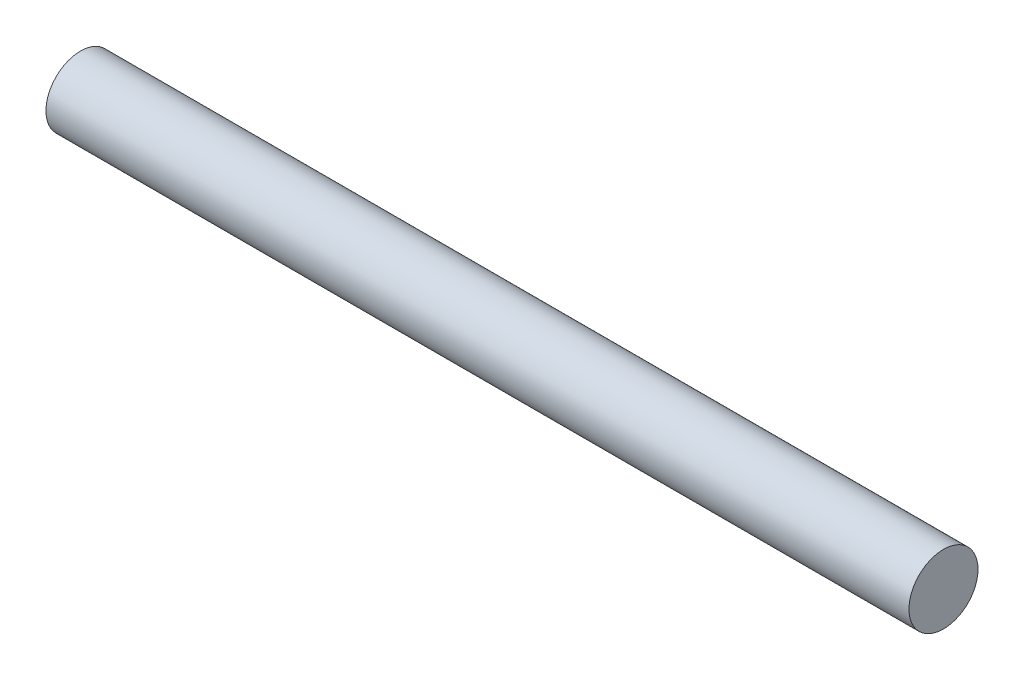
SolidWorks part; units mm, degrees
ref_plane "Front Plane" through (0, 0, 0) normal (0, 0, 1) x (1, 0, 0)
ref_plane "Top Plane" through (0, 0, 0) normal (0, 1, 0) x (1, 0, 0)
ref_plane "Right Plane" through (0, 0, 0) normal (1, 0, 0) x (0, 0, -1)
sketch "Sketch1" plane through (0, 0, 0) normal (1, 0, 0) x (0, 0, -1)
  circle A0 centre (0, 0) radius 4
  dimension "D1" = 8
extrude "Boss-Extrude1" add sketch "Sketch1" along normal blind 100
sketch "Sketch2" plane through (0, 0, 0) normal (0, 0, 1) x (1, 0, 0)
  line L0 (100, 0) -> (120.7431, 0)
  line L1 (100, -4) -> (100, 4) construction
sketch "Sketch3" plane through (100, 0, 0) normal (1, 0, 0) x (0, 0, -1)
  circle A0 centre (0, 0) radius 4
